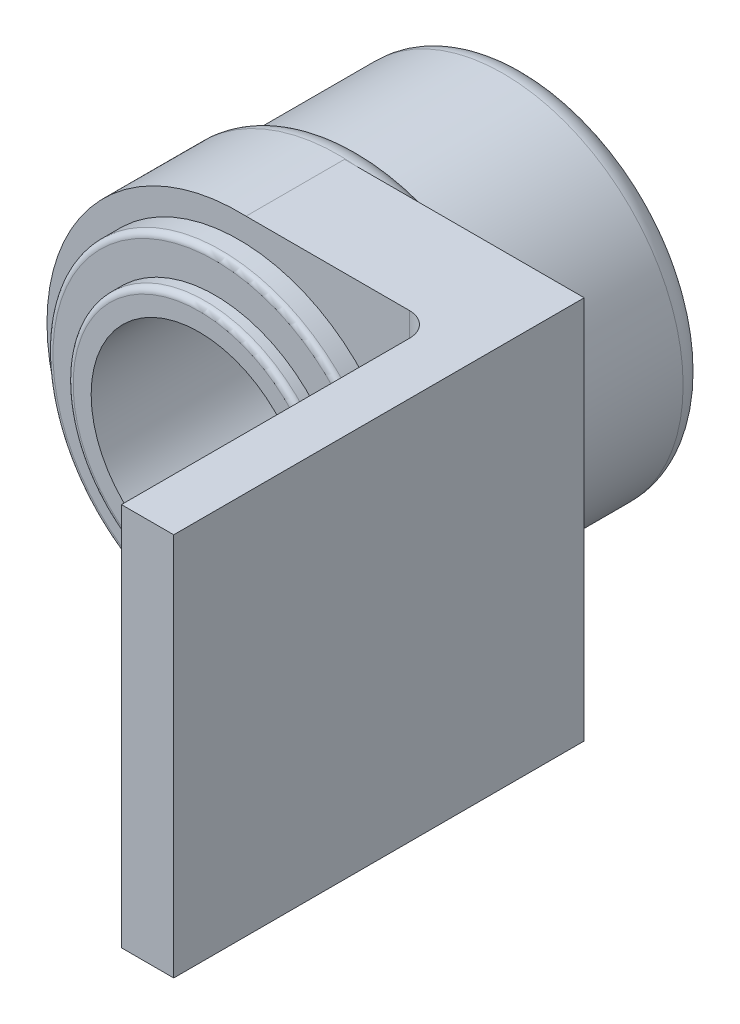
SolidWorks part; units mm, degrees
ref_plane "Front Plane" through (0, 0, 0) normal (0, 0, 1) x (1, 0, 0)
ref_plane "Top Plane" through (0, 0, 0) normal (0, 1, 0) x (1, 0, 0)
ref_plane "Right Plane" through (0, 0, 0) normal (1, 0, 0) x (0, 0, -1)
sketch "Sketch1" plane through (0, 0, 0) normal (0, 0, 1) x (1, 0, 0)
  circle A0 centre (0, 0) radius 19.05
  dimension "D1" = 38.1
extrude "Boss-Extrude1" add sketch "Sketch1" along normal blind 17.78 contours A0
sketch "Sketch2" plane through (0, 0, 0) normal (0, 0, -1) x (-1, 0, 0)
  circle A0 centre (0, 0) radius 10.16
  dimension "D1" = 20.32
extrude "Cut-Extrude1" cut sketch "Sketch2" against normal blind 1.27
fillet "Fillet1" radius 2.54 1 edges at (-10.16, 0, 0)
fillet "Fillet2" radius 2.54 1 edges at (19.05, 0, 0)
sketch "Sketch3" plane through (0, 0, 17.78) normal (0, 0, 1) x (1, 0, 0)
  circle A0 centre (0, 0) radius 20.32
  dimension "D1" = 40.64
extrude "Boss-Extrude2" add sketch "Sketch3" along normal blind 12.7 contours A0
fillet "Fillet3" radius 2.54 1 edges at (20.32, 0, 17.78)
sketch "Sketch4" plane through (0, 0, 30.48) normal (0, 0, 1) x (1, 0, 0)
  circle A0 centre (0, 0) radius 17.78
  dimension "D1" = 35.56
extrude "Boss-Extrude3" add sketch "Sketch4" along normal blind 2.54
sketch "Sketch5" plane through (0, 0, 33.02) normal (0, 0, 1) x (1, 0, 0)
  circle A0 centre (0, 0) radius 13.97
  dimension "D1" = 27.94
extrude "Boss-Extrude4" add sketch "Sketch5" along normal blind 1.6764
fillet "Fillet5" radius 0.635 2 edges at (17.78, 0, 33.02) (13.97, 0, 34.6964)
sketch "Sketch6" plane through (0, 0, 34.6964) normal (0, 0, 1) x (1, 0, 0)
  circle A0 centre (0, 0) radius 11.43
  dimension "D1" = 22.86
extrude "Cut-Extrude2" cut sketch "Sketch6" against normal blind 33.02
sketch "Sketch7" plane through (0, 0, 30.48) normal (0, 0, 1) x (1, 0, 0)
  line L0 (0.711, -20.3076) -> (26.111, -20.3076) construction
  line L1 (0.7438, 20.3064) -> (26.111, 20.3064) construction
  line L2 (26.111, 20.3064) -> (26.111, -20.3076) construction
  line L3 (0.711, -20.3076) -> (26.111, -20.3076)
  line L4 (26.111, -20.3076) -> (26.111, 20.3064)
  line L5 (26.111, 20.3064) -> (0.7438, 20.3064)
  line L6 (0.7438, 20.3064) -> (0.7438, 19.0364)
  line L7 (0.711, -20.3076) -> (0.711, -19.0376)
  circle A0 centre (0, 0) radius 20.32 construction
  spline S0 degree 3 poles (0.711, -19.0376) (10.7191, -19.8807) (29.9218, -0.3229) (10.7003, 19.399) (0.7438, 19.0364) knots 0 0 0 0 0.495917 1 1 1 1
  point P6 (20.3152, -0.4422)
  dimension "D1" = 25.4
  dimension "D2" = 1.27
  dimension "D3" = 1.27
extrude "Boss-Extrude6" add sketch "Sketch7" against normal blind 10.414
sketch "Sketch9" plane through (0, 0, 30.48) normal (0, 0, 1) x (1, 0, 0)
  line L0 (26.111, -16.0753) -> (23.0884, -16.0753) construction
  line L1 (26.111, -20.3076) -> (26.111, 20.3064) construction
  line L2 (17.5579, 0) -> (20.5805, 0) construction
  line L3 (0.711, -20.3076) -> (26.111, -20.3076) construction
  line L4 (20.5805, -20.3076) -> (26.111, -20.3076)
  line L5 (20.5805, -20.3076) -> (20.5805, 20.3064)
  line L6 (20.5805, 20.3064) -> (26.111, 20.3064)
  line L7 (26.111, -20.3076) -> (26.111, 20.3064)
  dimension "D1" = 3.0226
  dimension "D2" = 3.0226
extrude "Boss-Extrude7" add sketch "Sketch9" along normal blind 33.02
fillet "Fillet6" radius 2.54 1 edges at (20.5805, -0.0006, 30.48)
